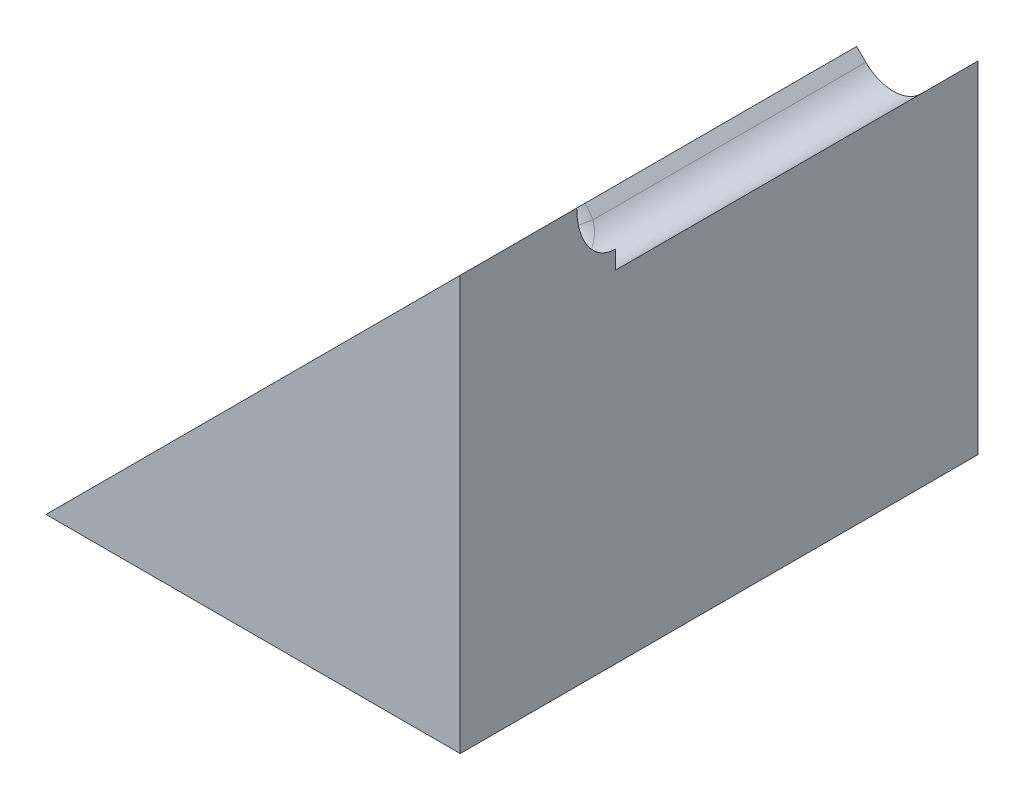
SolidWorks part; units mm, degrees
ref_plane "Front Plane" through (0, 0, 0) normal (0, 0, 1) x (1, 0, 0)
ref_plane "Top Plane" through (0, 0, 0) normal (0, 1, 0) x (1, 0, 0)
ref_plane "Right Plane" through (0, 0, 0) normal (1, 0, 0) x (0, 0, -1)
sketch "Sketch1" plane through (0, 0, 0) normal (0, 0, 1) x (1, 0, 0)
  line L0 (0, 0) -> (4, 4)
  line L1 (4, 4) -> (4, 0)
  line L2 (4, 0) -> (0, 0)
  dimension "D1" = 45
  dimension "D2" = 4
extrude "Boss-Extrude1" add sketch "Sketch1" along normal blind 5
ref_plane "Plane1" through (2, 2, 0) normal (0.7071, 0.7071, 0) x (0, 0, -1)
sketch "Sketch2" plane through (2, 2, 0) normal (0.7071, 0.7071, 0) x (0, 0, -1)
  line L0 (0, 0) -> (-5, 0) construction
  circle A0 centre (-3.5, 0) radius 0.375
  dimension "D1" = 0.75
  dimension "D2" = 3.5
extrude "Cut-Extrude1" cut sketch "Sketch2" against normal through all both and the other way through all
sketch "Sketch3" plane through (0, 0, 0) normal (-0.7071, 0.7071, 0) x (0, 0, 1)
  line L0 (5, 0) -> (3.875, 0) construction
  line L1 (0, 5.6569) -> (3.5, 5.6569)
  line L2 (0, 5.6569) -> (0, 4)
  line L3 (0, 4) -> (3.5, 4)
  line L4 (3.5, 5.6569) -> (3.5, 4)
  line L6 (0, 5.6569) -> (0, 0) construction
  arc A0 (3.125, 5.6569) -> (3.875, 5.6569) centre (3.5, 5.6569) ccw construction
  dimension "D1" = 4
extrude "Cut-Extrude3" cut sketch "Sketch3" against normal blind 0.5
fillet "Fillet1" radius 0.375 1 edges at (3.182, 2.4749, 1.75)
fillet "Fillet2" radius 0.5 2 edges at (3.0857, 2.6428, 3.2938) (2.8733, 2.7836, 3.1304)
